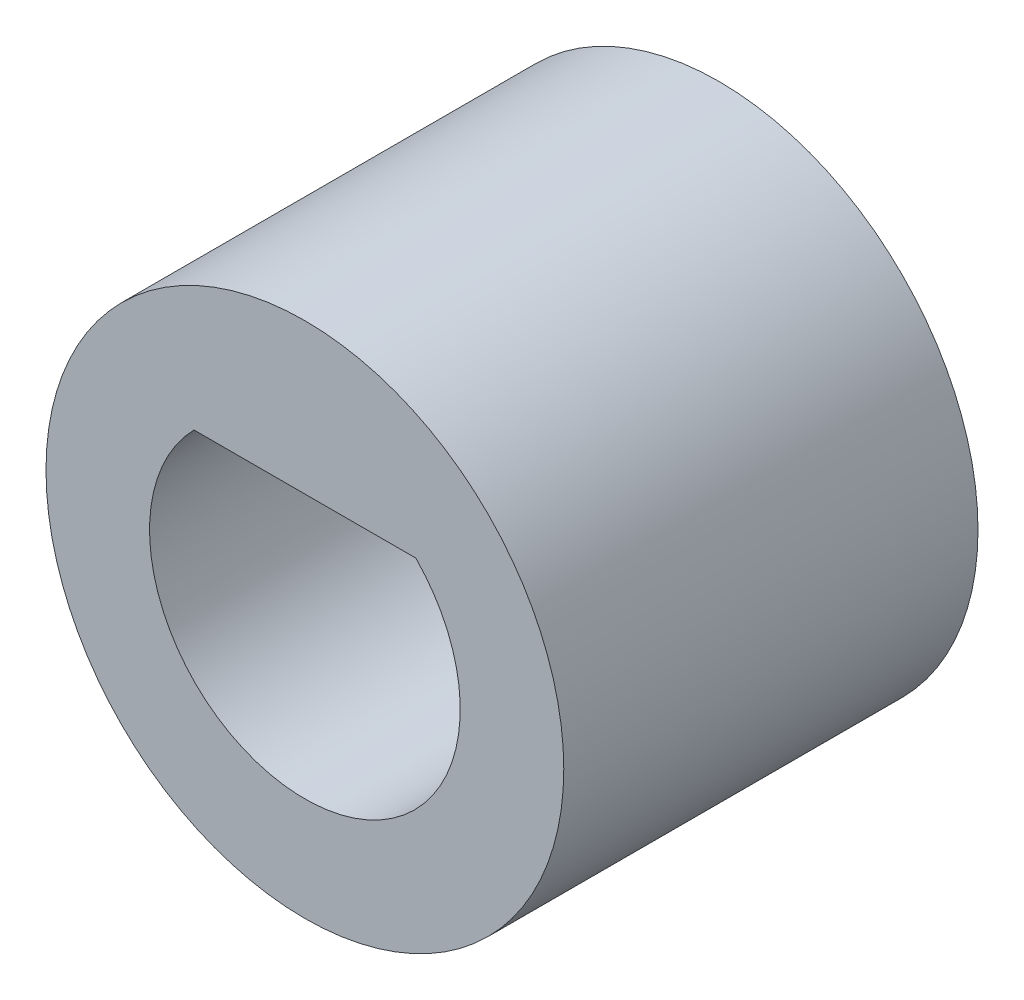
SolidWorks part; units mm, degrees
ref_plane "Plan de face" through (0, 0, 0) normal (0, 0, 1) x (1, 0, 0)
ref_plane "Plan de dessus" through (0, 0, 0) normal (0, 1, 0) x (1, 0, 0)
ref_plane "Plan de droite" through (0, 0, 0) normal (1, 0, 0) x (0, 0, -1)
sketch "Esquisse1" plane through (0, 0, 0) normal (0, 0, 1) x (1, 0, 0)
  line L0 (-2.1424, 2.1) -> (2.1424, 2.1)
  line L1 (-0.9885, -3) -> (1.037, -3) construction
  circle A0 centre (0, 0) radius 5
  arc A1 (-2.1424, 2.1) -> (2.1424, 2.1) centre (0, 0) ccw
  dimension "D1" = 10
  dimension "D2" = 6
  dimension "D3" = 5.1
extrude "Boss.-Extru.1" add sketch "Esquisse1" along normal blind 8
